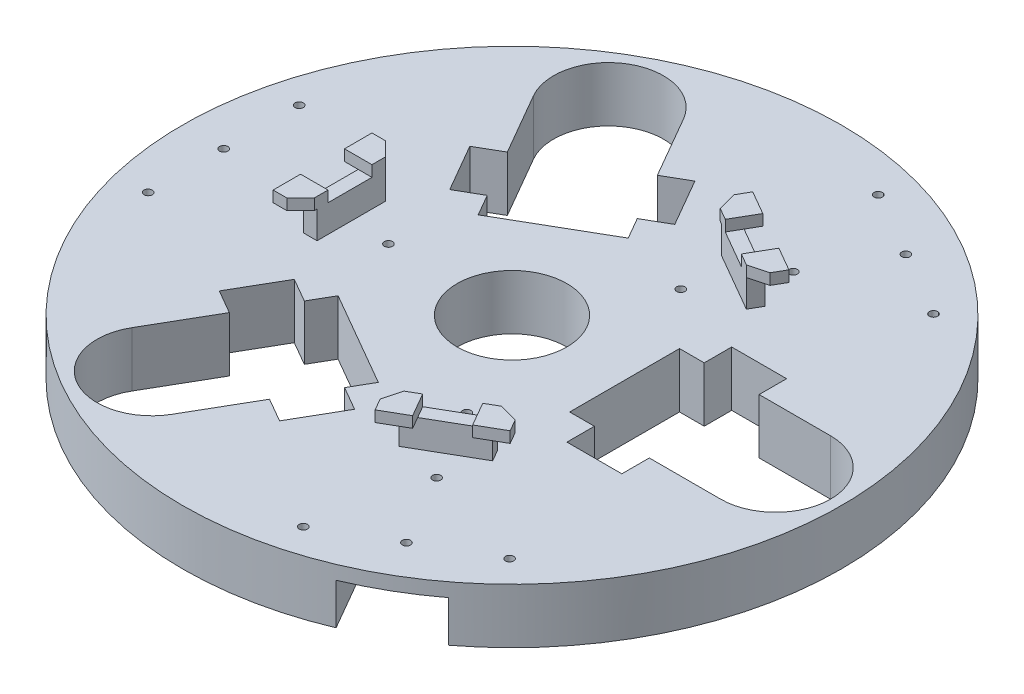
SolidWorks part; units mm, degrees
ref_plane "前视基准面" through (0, 0, 0) normal (0, 0, 1) x (1, 0, 0)
ref_plane "上视基准面" through (0, 0, 0) normal (0, 1, 0) x (1, 0, 0)
ref_plane "右视基准面" through (0, 0, 0) normal (1, 0, 0) x (0, 0, -1)
sketch "草图1" plane through (0, 0, 0) normal (0, 1, 0) x (1, 0, 0)
  circle A0 centre (0, 0) radius 120
  dimension "D1" = 240
extrude "凸台-拉伸1" add sketch "草图1" along normal blind 20
sketch "草图2" plane through (0, 20, 0) normal (0, 1, 0) x (1, 0, 0)
  circle A0 centre (60, 0) radius 15
  circle A1 centre (-30, -51.9615) radius 15
  circle A2 centre (-30, 51.9615) radius 15
  dimension "D1" = 30
  dimension "D2" = 60
  dimension "D3" = 3
extrude "切除-拉伸1" cut sketch "草图2" against normal through all both and the other way through all
ref_plane "基准面4" through (0, 10, 0) normal (0, 1, 0) x (1, 0, 0)
ref_axis "基准轴1" through (0, 0, 0) along (0, 1, 0)
sketch "草图3" plane through (0, 10, 0) normal (0, 1, 0) x (1, 0, 0)
  line L0 (0, 0) -> (200, 0) construction
  line L1 (0, 0) -> (100, -173.2051) construction
  line L2 (0, 0) -> (-100, -173.2051) construction
  line L3 (0, 0) -> (-200, 0) construction
  line L4 (0, 0) -> (-100, 173.2051) construction
  line L5 (0, 0) -> (100, 173.2051) construction
  line L6 (200, 0) -> (200, -115.4701) construction
  line L7 (200, -115.4701) -> (100, -173.2051) construction
  line L8 (100, -173.2051) -> (0, -230.9401) construction
  line L9 (0, -230.9401) -> (-100, -173.2051) construction
  line L10 (-100, -173.2051) -> (-200, -115.4701) construction
  line L11 (-200, -115.4701) -> (-200, 0) construction
  line L12 (-200, 0) -> (-200, 115.4701) construction
  line L13 (-200, 115.4701) -> (-100, 173.2051) construction
  line L14 (-100, 173.2051) -> (0, 230.9401) construction
  line L15 (0, 230.9401) -> (100, 173.2051) construction
  line L16 (100, 173.2051) -> (200, 115.4701) construction
  line L17 (200, 115.4701) -> (200, 0) construction
  dimension "D2" = 200
  dimension "D1" = 6
sketch "草图4" plane through (0, 0, 0) normal (0, -1, 0) x (1, 0, 0)
  line L0 (7.0096, 42.141) -> (32.9904, 27.141)
  line L1 (7.0096, 42.141) -> (57.0096, 128.7436)
  line L2 (32.9904, 27.141) -> (82.9904, 113.7436)
  line L3 (57.0096, 128.7436) -> (82.9904, 113.7436)
  line L4 (0, 0) -> (100, 173.2051) construction
  point P7 (20, 34.641)
  dimension "D1" = 100
  dimension "D2" = 30
  dimension "D3" = 15
  dimension "D4" = 40
extrude "切除-拉伸2" cut sketch "草图4" against normal blind 15
ref_axis "基准轴2" through (0, 0, 0) along (0, 1, 0)
pattern_circular "阵列(圆周)1" count 3 every 120 about axis through (0, 0, 0) along (0, 1, 0) of "切除-拉伸2"
sketch "草图5" plane through (0, 0, 0) normal (0, -1, 0) x (1, 0, 0)
  line L0 (0, 0) -> (-200, 0) construction
  circle A0 centre (-45, 0) radius 1.5
  circle A1 centre (-75, 0) radius 1.5
  circle A2 centre (-105, 0) radius 1.5
  dimension "D1" = 3
  dimension "D2" = 45
  dimension "D4" = 30
  dimension "D3" = 3
extrude "切除-拉伸3" cut sketch "草图5" against normal through all both and the other way through all
pattern_circular "阵列(圆周)2" count 3 every 120 about axis through (0, 0, 0) along (0, 1, 0) of "切除-拉伸3"
sketch "草图6" plane through (0, 20, 0) normal (0, 1, 0) x (1, 0, 0)
  line L0 (41, 20) -> (41, -20)
  line L1 (41, -20) -> (50, -20)
  line L2 (41, 20) -> (50, 20)
  line L3 (0, 0) -> (200, 0) construction
  line L4 (50, 30) -> (50, 20)
  line L5 (50, 30) -> (70, 30)
  line L6 (70, 30) -> (70, 20)
  line L7 (70, 20) -> (96, 20)
  line L8 (50, -30) -> (70, -30)
  line L9 (70, -30) -> (70, -20)
  line L10 (50, -30) -> (50, -20)
  line L11 (70, -20) -> (96, -20)
  arc A0 (96, -20) -> (96, 20) centre (96, 0) ccw
  circle A2 centre (60, 0) radius 15 construction
  point P11 (60, 30)
  point P18 (60, -30)
  dimension "D5" = 20
  dimension "D1" = 40
  dimension "D2" = 20
  dimension "D3" = 19
  dimension "D4" = 55
  dimension "D6" = 20
  dimension "D7" = 0
  dimension "D8" = 30
  dimension "D9" = 20
  dimension "D10" = 0
  dimension "D11" = 30
extrude "切除-拉伸4" cut sketch "草图6" against normal through all both and the other way through all
pattern_circular "阵列(圆周)3" count 3 every 120 about axis through (0, 0, 0) along (0, 1, 0) of "切除-拉伸4"
sketch "草图7" plane through (0, 20, 0) normal (0, 1, 0) x (1, 0, 0)
  circle A0 centre (0, 0) radius 20
  dimension "D1" = 40
extrude "切除-拉伸5" cut sketch "草图7" against normal through all
sketch "草图8" plane through (0, 20, 0) normal (0, 1, 0) x (1, 0, 0)
  line L0 (0, 0) -> (-160.7766, 0) construction
  line L1 (-105, 27.5) -> (-105, -27.5) construction
  circle A0 centre (-105, 27.5) radius 1.5
  circle A1 centre (-105, -27.5) radius 1.5
  dimension "D4" = 3
  dimension "D5" = 3
  dimension "D1" = 55
  dimension "D2" = 27.5
  dimension "D3" = 105
extrude "切除-拉伸6" cut sketch "草图8" against normal through all both and the other way through all
sketch "草图9" plane through (0, 20, 0) normal (0, 1, 0) x (1, 0, 0)
  line L0 (-30, 10) -> (-30, -10)
  line L1 (-30, -10) -> (-35, -10)
  line L2 (-35, -10) -> (-35, 10)
  line L3 (-35, 10) -> (-30, 10)
  dimension "D1" = 20
  dimension "D2" = 5
  dimension "D3" = 30
  dimension "D4" = 10
extrude "凸台-拉伸2" [suppressed] add sketch "草图9" along normal blind 10
pattern_circular "阵列(圆周)4" count 3 every 120 about axis through (0, 0, 0) along (0, 1, 0) of "切除-拉伸6", "凸台-拉伸2" reverse direction yes
sketch "草图12" plane through (0, 20, 0) normal (0, 1, 0) x (1, 0, 0)
  line L0 (-64, 13) -> (-64, -12)
  line L1 (-64, -12) -> (-59, -12)
  line L2 (-59, -12) -> (-59, 13)
  line L3 (-59, 13) -> (-64, 13)
  dimension "D1" = 64
  dimension "D2" = 25
  dimension "D3" = 13
  dimension "D4" = 5
extrude "凸台-拉伸3" add sketch "草图12" along normal blind 10
sketch "草图13" plane through (0, 30, 0) normal (0, 1, 0) x (1, 0, 0)
  line L0 (-69, 8) -> (-59, 8)
  line L1 (-59, -13) -> (-59, -8)
  line L2 (-69, 8) -> (-69, 18)
  line L3 (-69, 18) -> (-64, 18)
  line L4 (-64, 18) -> (-59, 13)
  line L5 (-59, 13) -> (-59, 8)
  line L6 (-59, -12) -> (-59, 13) construction
  line L7 (0, 0) -> (-180.3971, 0) construction
  line L8 (-64, -18) -> (-59, -13)
  line L9 (-69, -18) -> (-64, -18)
  line L10 (-69, -8) -> (-69, -18)
  line L11 (-69, -8) -> (-59, -8)
  dimension "D1" = 8
  dimension "D2" = 10
  dimension "D3" = 10
  dimension "D4" = 5
extrude "凸台-拉伸4" add sketch "草图13" along normal blind 4
pattern_circular "阵列(圆周)5" count 3 every 120 about axis through (0, 0, 0) along (0, 1, 0) of "凸台-拉伸3", "凸台-拉伸4"
